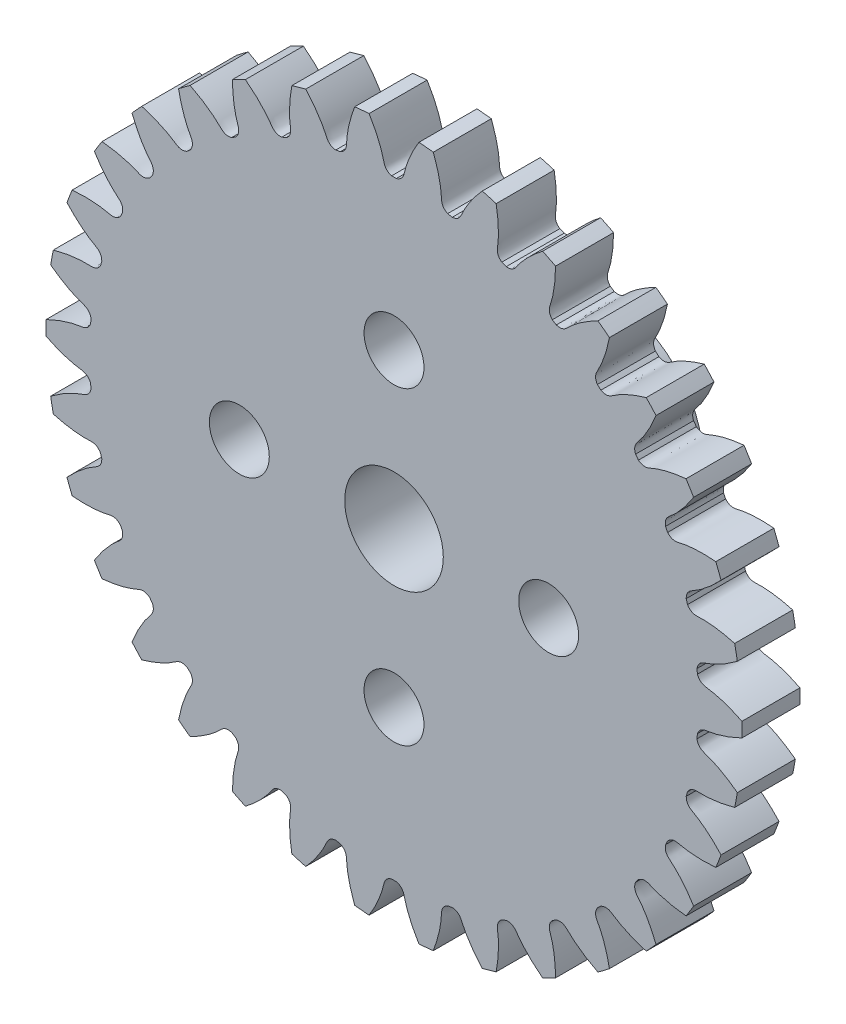
SolidWorks part; units mm, degrees
material "Thornel Mat VMA"
ref_plane "前视基准面" through (0, 0, 0) normal (0, 0, 1) x (1, 0, 0)
ref_plane "上视基准面" through (0, 0, 0) normal (0, 1, 0) x (1, 0, 0)
ref_plane "右视基准面" through (0, 0, 0) normal (1, 0, 0) x (0, 0, -1)
sketch "草图1" plane through (0, 0, 0) normal (0, 0, 1) x (1, 0, 0)
  circle A0 centre (0, 0) radius 18
extrude "凸台-拉伸1" add sketch "草图1" along normal blind 5
ref_axis "基准轴1" through (0, 0, 5) along (0, 0, -1)
sketch "草图2" plane through (0, 0, 0) normal (0, 0, 1) x (1, 0, 0)
  line L0 (0, 0) -> (0, 18) construction
  circle A0 centre (0, 0) radius 18 construction
  arc A1 (0.1221, 15.7495) -> (-0.1221, 15.7495) centre (0, 0) ccw
  arc A2 (3.3716, 20.3699) -> (-3.3716, 20.3699) centre (0, 0) ccw
  spline S0 degree 3 poles (0.1221, 15.7495) (0.4777, 15.8501) (0.5089, 16.1259) (0.5866, 16.4158) (0.6086, 16.4922) (0.6341, 16.5742) (0.6631, 16.6618) (0.6961, 16.7548) (0.7331, 16.8531) (0.7745, 16.9566) (0.8205, 17.0651) (0.8712, 17.1786) (0.9269, 17.2967) (0.9877, 17.4195) (1.054, 17.5467) (1.1259, 17.6781) (1.2035, 17.8136) (1.2872, 17.953) (1.377, 18.0962) (1.4731, 18.2428) (1.5758, 18.3928) (1.6852, 18.5459) (1.8014, 18.7019) (1.9246, 18.8606) (2.055, 19.0217) (2.1928, 19.1851) (2.3379, 19.3506) (2.4907, 19.5178) (2.6512, 19.6865) (2.8195, 19.8566) (3.0576, 20.0877) (3.2437, 20.2577) (3.3716, 20.3699) knots 0 0 0 0 0.130724 0.143504 0.157401 0.172415 0.188546 0.205794 0.224159 0.243641 0.26424 0.285956 0.308788 0.332738 0.357805 0.383988 0.411289 0.439706 0.46924 0.499892 0.53166 0.564545 0.598547 0.633666 0.669902 0.707255 0.745725 0.785312 0.826016 0.867836 0.910774 1 1 1 1
  spline S1 degree 3 poles (-0.1221, 15.7495) (-0.4777, 15.8501) (-0.5089, 16.1259) (-0.5866, 16.4158) (-0.6086, 16.4922) (-0.6341, 16.5742) (-0.6631, 16.6618) (-0.6961, 16.7548) (-0.7331, 16.8531) (-0.7745, 16.9566) (-0.8205, 17.0651) (-0.8712, 17.1786) (-0.9269, 17.2967) (-0.9877, 17.4195) (-1.054, 17.5467) (-1.1259, 17.6781) (-1.2035, 17.8136) (-1.2872, 17.953) (-1.377, 18.0962) (-1.4731, 18.2428) (-1.5758, 18.3928) (-1.6852, 18.5459) (-1.8014, 18.7019) (-1.9246, 18.8606) (-2.055, 19.0217) (-2.1928, 19.1851) (-2.3379, 19.3506) (-2.4907, 19.5178) (-2.6512, 19.6865) (-2.8195, 19.8566) (-3.0576, 20.0877) (-3.2437, 20.2577) (-3.3716, 20.3699) knots 0 0 0 0 0.130724 0.143504 0.157401 0.172415 0.188546 0.205794 0.224159 0.243641 0.26424 0.285956 0.308788 0.332738 0.357805 0.383988 0.411289 0.439706 0.46924 0.499892 0.53166 0.564545 0.598547 0.633666 0.669902 0.707255 0.745725 0.785312 0.826016 0.867836 0.910774 1 1 1 1
extrude "切除-拉伸1" cut sketch "草图2" along normal through all
pattern_circular "阵列(圆周)1" count 34 every 10.588 about axis through (0, 0, 5) along (0, 0, -1) of "切除-拉伸1"
sketch "草图3" plane through (0, 0, 0) normal (0, 0, 1) x (1, 0, 0)
  circle A0 centre (0, 0) radius 17 construction
  dimension "Dn" = 34
ref_plane "基准面1" through (0, 0, 5) normal (0, 0, 1) x (1, 0, 0)
sketch "草图4" plane through (0, 0, 5) normal (0, 0, 1) x (1, 0, 0)
  circle A0 centre (0, 0) radius 2.55
  circle A1 centre (0, 0) radius 8 construction
  circle A2 centre (8, 0) radius 1.55
  circle A3 centre (0, -8) radius 1.55
  circle A4 centre (-8, 0) radius 1.55
  circle A5 centre (0, 8) radius 1.55
  point P15 (0, 0)
  dimension "D1" = 5.1
  dimension "D2" = 16
  dimension "D3" = 3.1
  dimension "D4" = 4
extrude "切除-拉伸2" cut sketch "草图4" against normal blind 10
ref_plane "基准面2" through (0, 0, 5) normal (0, 0, 1) x (1, 0, 0)
sketch "草图5" plane through (0, 0, 5) normal (0, 0, 1) x (1, 0, 0)
  circle A0 centre (-132.5995, 117.3916) radius 416.7363
extrude "切除-拉伸3" cut sketch "草图5" against normal blind 2
sketch "草图6" plane through (0, 0, 0) normal (0, 0, -1) x (-1, 0, 0)
  circle A0 centre (0, 0) radius 2.55
  circle A1 centre (0, 0) radius 5
extrude "凸台-拉伸2" add sketch "草图6" along normal blind 8
ref_plane "基准面3" through (-4.5112, 2.1563, 0) normal (-0.9022, 0.4313, 0) x (0, 0, 1)
sketch "草图8" plane through (-4.5112, 2.1563, 0) normal (-0.9022, 0.4313, 0) x (0, 0, 1)
  circle A0 centre (-4.5231, 0) radius 1.6
extrude "切除-拉伸4" cut sketch "草图8" against normal blind 10
fillet "圆角1" radius 2 1 edges at (5, 0, 0)
